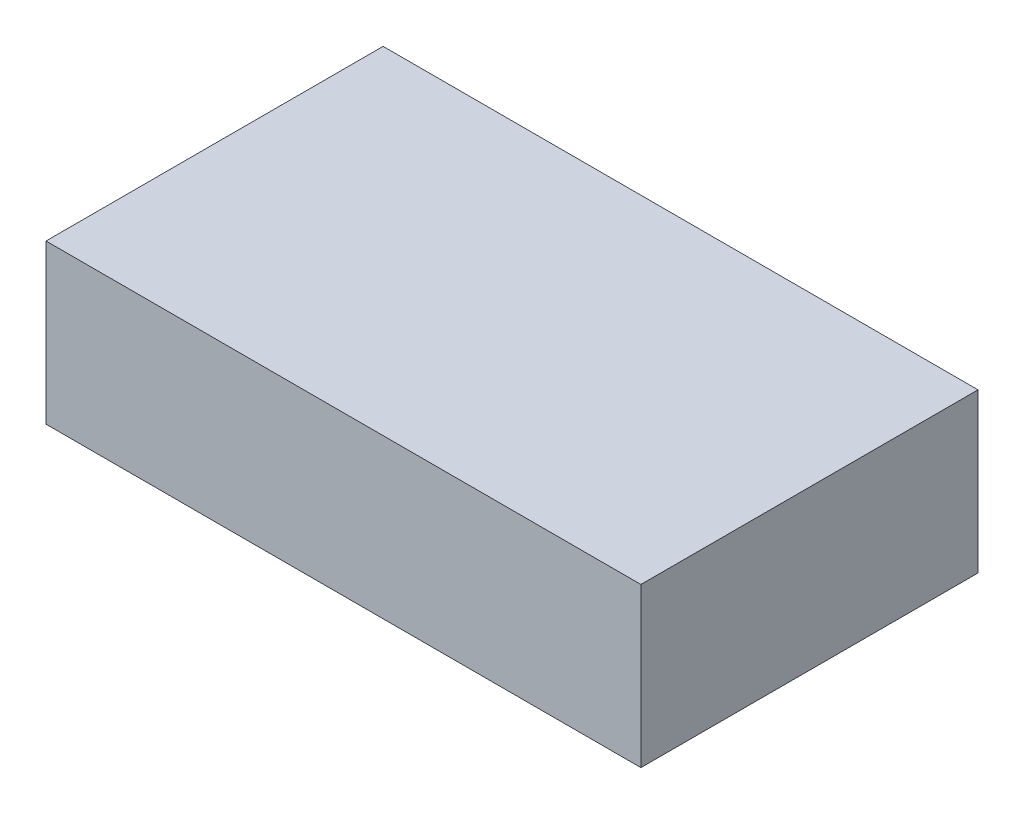
SolidWorks part; units mm, degrees
ref_plane "Front Plane" through (0, 0, 0) normal (0, 0, 1) x (1, 0, 0)
ref_plane "Top Plane" through (0, 0, 0) normal (0, 1, 0) x (1, 0, 0)
ref_plane "Right Plane" through (0, 0, 0) normal (1, 0, 0) x (0, 0, -1)
sketch "Sketch1" plane through (0, 0, 0) normal (0, 1, 0) x (1, 0, 0)
  line L1 (0, 0) -> (381, 0)
  line L2 (0, 0) -> (0, 215.9)
  line L3 (0, 215.9) -> (381, 215.9)
  line L4 (381, 0) -> (381, 215.9)
  dimension "D1" = 381
  dimension "D2" = 215.9
extrude "Boss-Extrude1" add sketch "Sketch1" along normal blind 101.6
